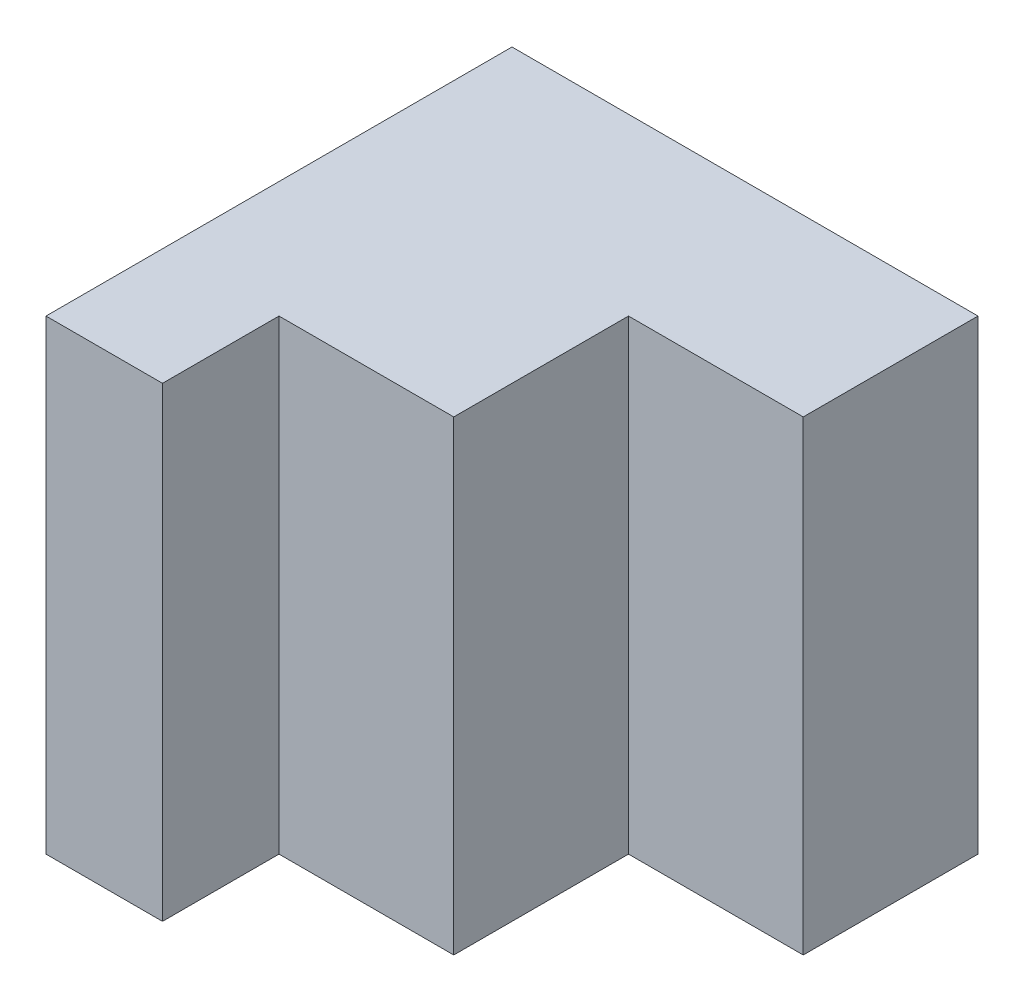
SolidWorks part; units mm, degrees
ref_plane "Front Plane" through (0, 0, 0) normal (0, 0, 1) x (1, 0, 0)
ref_plane "Top Plane" through (0, 0, 0) normal (0, 1, 0) x (1, 0, 0)
ref_plane "Right Plane" through (0, 0, 0) normal (1, 0, 0) x (0, 0, -1)
sketch "Sketch1" plane through (0, 0, 0) normal (0, 0, 1) x (1, 0, 0)
  line L0 (-30, 40) -> (-30, 0)
  line L1 (-40, 0) -> (0, 0)
  line L2 (-40, 0) -> (-40, 40)
  line L3 (-40, 40) -> (0, 40)
  line L4 (0, 0) -> (0, 40)
  line L5 (-15, 40) -> (-15, 0)
  point P8 (0, 0)
  dimension "D1" = 40
  dimension "D2" = 10
  dimension "D3" = 15
  dimension "D4" = 40
extrude "Boss-Extrude3" add sketch "Sketch1" along normal blind 40 contours L3 L2 L1 L0 region at (-35, 20, 0)
extrude "Boss-Extrude4" add sketch "Sketch1<5>" along normal blind 30 contours L5 L3 L0 L1 region at (-22.5, 20, 0)
sketch "Sketch1<5>" plane through (0, 0, 0) normal (0, 0, 1) x (1, 0, 0) same geometry as "Sketch1"
extrude "Boss-Extrude5" add sketch "Sketch1<6>" along normal blind 15 contours L3 L5 L1 L4 region at (-7.5, 20, 0)
sketch "Sketch1<6>" plane through (0, 0, 0) normal (0, 0, 1) x (1, 0, 0) same geometry as "Sketch1"
